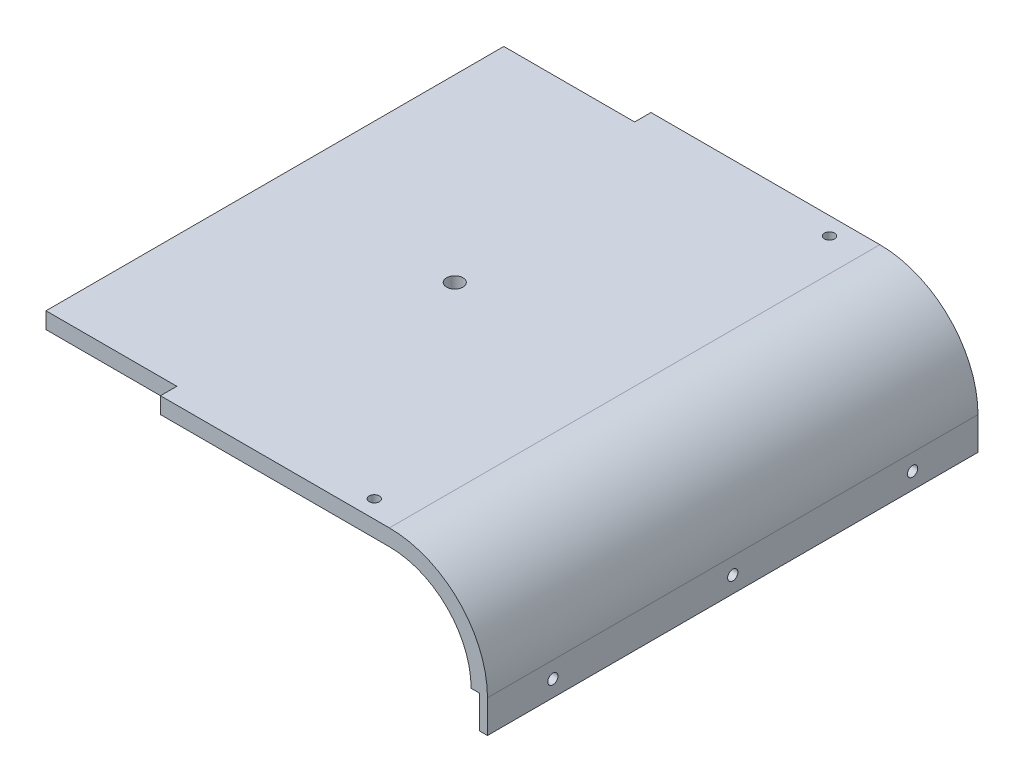
SolidWorks part; units mm, degrees
ref_plane "Front Plane" through (0, 0, 0) normal (0, 0, 1) x (1, 0, 0)
ref_plane "Top Plane" through (0, 0, 0) normal (0, 1, 0) x (1, 0, 0)
ref_plane "Right Plane" through (0, 0, 0) normal (1, 0, 0) x (0, 0, -1)
sketch "Sketch1" plane through (0, 0, 0) normal (0, 0, 1) x (1, 0, 0)
  line L0 (-139.7, 0) -> (139.7, 0)
  line L1 (139.7, 0) -> (139.7, -152.4) construction
  line L2 (139.7, -76.2) -> (215.9, -76.2) construction
  line L3 (-139.7, -12.7) -> (139.7, -12.7)
  line L4 (-139.7, 0) -> (-139.7, -12.7)
  line L5 (215.9, -76.2) -> (203.2, -76.2)
  circle A0 centre (139.7, -76.2) radius 76.2 construction
  arc A1 (139.7, 0) -> (215.9, -76.2) centre (139.7, -76.2) cw
  arc A2 (139.7, -12.7) -> (203.2, -76.2) centre (139.7, -76.2) cw
  point P4 (0, 0)
  dimension "D1" = 152.4
  dimension "D2" = 355.6
  dimension "D3" = 12.7
extrude "Boss-Extrude1" add sketch "Sketch1" along normal blind 190.5 and the other way blind 190.5
sketch "Sketch2" plane through (0, -76.2, 0) normal (0, -1, 0) x (1, 0, 0)
  line L0 (203.2, 190.5) -> (215.9, 190.5) construction
  line L1 (209.55, 190.5) -> (215.9, 190.5)
  line L2 (209.55, 190.5) -> (209.55, -190.5)
  line L3 (209.55, -190.5) -> (215.9, -190.5)
  line L4 (215.9, 190.5) -> (215.9, -190.5)
extrude "Boss-Extrude2" add sketch "Sketch2" along normal blind 25.4
sketch "Sketch3" plane through (215.9, 0, 0) normal (1, 0, 0) x (0, 0, -1)
  line L0 (-190.5, -88.9) -> (190.5, -88.9) construction
  line L1 (-190.5, -101.6) -> (-190.5, -76.2) construction
  line L2 (190.5, -101.6) -> (190.5, -76.2) construction
  line L3 (0, -76.2) -> (0, -101.6) construction
  line L4 (190.5, -76.2) -> (-190.5, -76.2) construction
  line L5 (190.5, -101.6) -> (-190.5, -101.6) construction
  line L6 (139.7, -76.2) -> (139.7, -101.6) construction
  line L7 (-139.7, -76.2) -> (-139.7, -101.6) construction
  circle A0 centre (-139.7, -88.9) radius 3.9687
  circle A1 centre (0, -88.9) radius 3.9687
  circle A2 centre (139.7, -88.9) radius 3.9687
  dimension "D3" = 7.9375
  dimension "D1" = 139.7
  dimension "D2" = 139.7
extrude "Cut-Extrude1" cut sketch "Sketch3" against normal blind 25.4
sketch "Sketch4" plane through (0, 0, 0) normal (0, 1, 0) x (1, 0, 0)
  circle A0 centre (0, 0) radius 6.35
  dimension "D1" = 12.7
extrude "Cut-Extrude2" cut sketch "Sketch4" against normal blind 17.78
sketch "Sketch5" plane through (0, 0, 0) normal (0, 1, 0) x (1, 0, 0)
  line L0 (139.7, 0) -> (114.3, 0) construction
  line L1 (139.7, 190.5) -> (139.7, -190.5) construction
  line L2 (-139.7, 190.5) -> (-139.7, -190.5) construction
  line L3 (0, 177.8) -> (0, -177.8) construction
  line L4 (114.3, 177.8) -> (114.3, -177.8) construction
  line L5 (-114.3, -177.8) -> (-114.3, 177.8) construction
  line L6 (139.7, -190.5) -> (-139.7, -190.5) construction
  line L7 (-114.3, 0) -> (-139.7, 0) construction
  line L8 (-114.3, 0) -> (0, 0) construction
  line L9 (0, 0) -> (114.3, 0) construction
  line L12 (-114.3, -177.8) -> (-139.7, -177.8)
  line L13 (-139.7, -177.8) -> (-139.7, -190.5)
  line L14 (-139.7, -190.5) -> (-38.1, -190.5)
  line L15 (-38.1, -190.5) -> (-38.1, -177.8)
  line L16 (-38.1, -177.8) -> (-114.3, -177.8)
  line L27 (-38.1, 190.5) -> (-38.1, 177.8)
  line L28 (-139.7, 190.5) -> (-38.1, 190.5)
  line L29 (-139.7, 177.8) -> (-139.7, 190.5)
  line L30 (-114.3, 177.8) -> (-139.7, 177.8)
  line L31 (-38.1, 177.8) -> (-114.3, 177.8)
  line L32 (139.7, 190.5) -> (-139.7, 190.5) construction
  circle A3 centre (114.3, -176.784) radius 3.937
  circle A4 centre (114.3, 176.784) radius 3.937
  point P11 (0, 0)
  point P15 (114.3, 0)
  point P18 (-114.3, 0)
  dimension "D3" = 13.716
  dimension "D2" = 7.874
  dimension "D1" = 12.7
  dimension "D4" = 101.6
  dimension "D5" = 13.716
  dimension "D6" = 114.3
extrude "Cut-Extrude3" cut sketch "Sketch5" against normal through all
